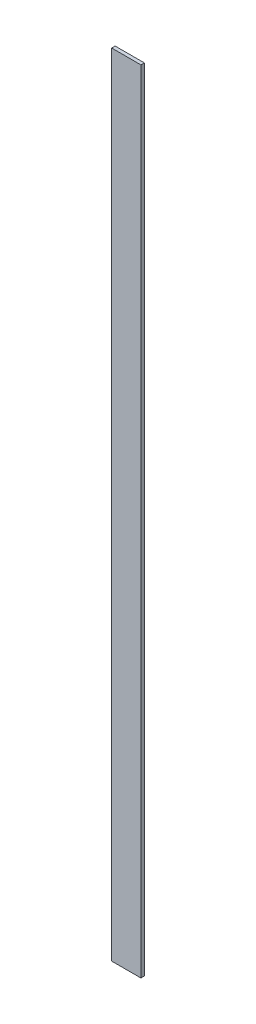
SolidWorks part; units mm, degrees
material "Copper"
ref_plane "Front Plane" through (0, 0, 0) normal (0, 0, 1) x (1, 0, 0)
ref_plane "Top Plane" through (0, 0, 0) normal (0, 1, 0) x (1, 0, 0)
ref_plane "Right Plane" through (0, 0, 0) normal (1, 0, 0) x (0, 0, -1)
sketch "Sketch1" plane through (0, 0, 0) normal (0, 0, 1) x (1, 0, 0)
  line L1 (-3.7961, 15.8034) -> (4.7039, 15.8034)
  line L2 (-3.7961, 15.8034) -> (-3.7961, -214.1966)
  line L3 (-3.7961, -214.1966) -> (4.7039, -214.1966)
  line L4 (4.7039, 15.8034) -> (4.7039, -214.1966)
  dimension "D1" = 8.5
  dimension "D2" = 230
base flange "Base-Flange1" sketch "Sketch1" thickness 1 reverse thickness direction no parameters "D1"=1
sketch "Bend-Lines1" [suppressed] plane through (0, 0, 0) normal (0, 1, 0) x (1, 0, 0)
sketch "Bounding-Box1" [suppressed] plane through (0, 0, 0) normal (0, 1, 0) x (1, 0, 0)
sheet metal parameters "Sheet-Metal1" thickness 1 parameters "D1"=1
flat pattern "Flat-Pattern1" [suppressed]
sketch "Bend-Lines2" plane through (0, 0, 0) normal (0, 1, 0) x (1, 0, 0)
sketch3d "Bounding-Box2" [suppressed]
  line L0 (-4.7039, 15.8034, 0) -> (-4.7039, -214.1966, 0) construction
  line L1 (3.7961, 15.8034, 0) -> (3.7961, -214.1966, 0) construction
  line L2 (-4.7039, 15.8034, 0) -> (3.7961, 15.8034, 0) construction
  line L3 (-4.7039, -214.1966, 0) -> (3.7961, -214.1966, 0) construction
